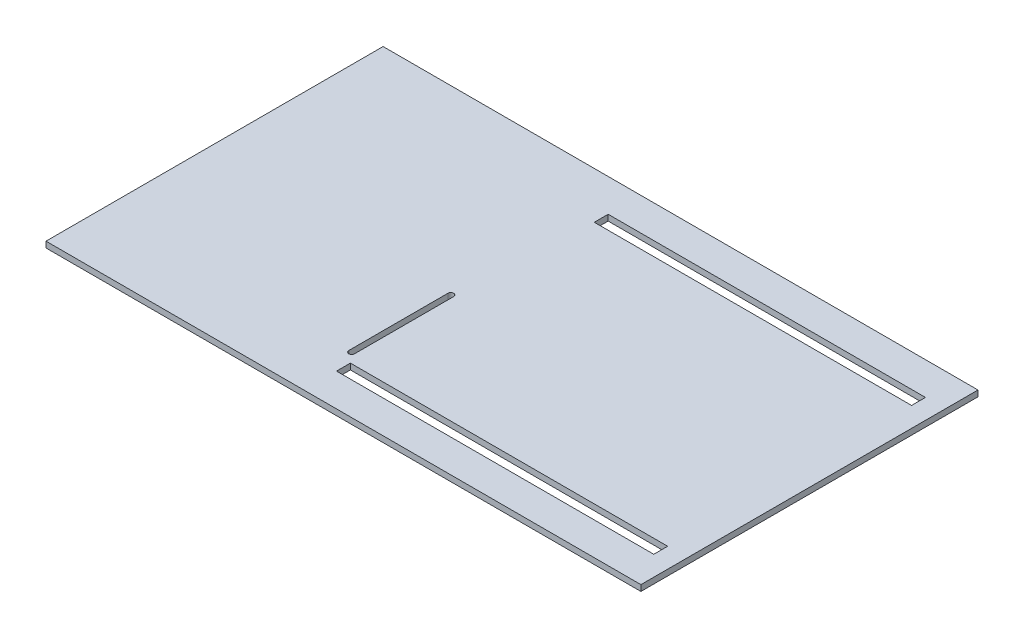
SolidWorks part; units mm, degrees
ref_plane "정면" through (0, 0, 0) normal (0, 0, 1) x (1, 0, 0)
ref_plane "윗면" through (0, 0, 0) normal (0, 1, 0) x (1, 0, 0)
ref_plane "우측면" through (0, 0, 0) normal (1, 0, 0) x (0, 0, -1)
sketch "스케치1" plane through (0, 0, 0) normal (0, 1, 0) x (1, 0, 0)
  line L1 (0, 0) -> (300, 0)
  line L2 (0, 0) -> (0, 170)
  line L3 (0, 170) -> (300, 170)
  line L4 (300, 0) -> (300, 170)
  dimension "D1" = 170
  dimension "D2" = 300
extrude "보스-돌출1" add sketch "스케치1" along normal blind 3
sketch "스케치2" plane through (0, 3, 0) normal (0, 1, 0) x (1, 0, 0)
  line L0 (138, 53.6066) -> (93.0904, 53.6066) construction
  line L1 (138, 51.1066) -> (138, 56.1066) construction
  line L3 (124.1, 53.6066) -> (124.1, 78.6066)
  line L4 (124.1, 28.6066) -> (127, 28.6066)
  line L5 (124.1, 28.6066) -> (124.1, 53.6066)
  line L6 (124.1, 78.6066) -> (127, 78.6066)
  line L7 (127, 28.6066) -> (127, 78.6066)
  line L8 (125.1, 73.7292) -> (125.1, 75.9866) construction
  line L10 (126, 73.7292) -> (126, 75.9866) construction
  dimension "D1" = 1
  dimension "D2" = 1
  dimension "D3" = 25
  dimension "D4" = 25
extrude "컷-돌출1" cut sketch "스케치2" against normal blind 10
sketch "스케치3" plane through (0, 3, 0) normal (0, 1, 0) x (1, 0, 0)
  line L0 (127, 78.6066) -> (124.1, 78.6066) construction
  line L1 (124.1, 28.6066) -> (127, 28.6066) construction
  circle A0 centre (125.55, 78.6066) radius 1.45
  circle A1 centre (125.55, 28.6066) radius 1.45
extrude "컷-돌출2" cut sketch "스케치3" against normal blind 10
sketch "스케치4" plane through (0, 3, 0) normal (0, 1, 0) x (1, 0, 0)
  line L0 (262.566, 152.5) -> (279.4264, 152.5) construction
  line L1 (290, 153.5) -> (130, 153.5)
  line L2 (290, 153.5) -> (290, 146.5)
  line L3 (290, 146.5) -> (130, 146.5)
  line L4 (130, 153.5) -> (130, 146.5)
  line L5 (130, 16.5) -> (290, 16.5)
  line L6 (130, 16.5) -> (130, 23.5)
  line L7 (130, 23.5) -> (290, 23.5)
  line L8 (290, 16.5) -> (290, 23.5)
  line L9 (262.566, 147.5) -> (279.4264, 147.5) construction
  line L10 (262.566, 22.5) -> (279.4264, 22.5) construction
  line L11 (300, 0) -> (300, 170) construction
  line L12 (0, 170) -> (0, 0) construction
  dimension "D1" = 1
  dimension "D2" = 1
  dimension "D3" = 1
  dimension "D4" = 10
  dimension "D5" = 130
extrude "컷-돌출3" cut sketch "스케치4" against normal blind 10
